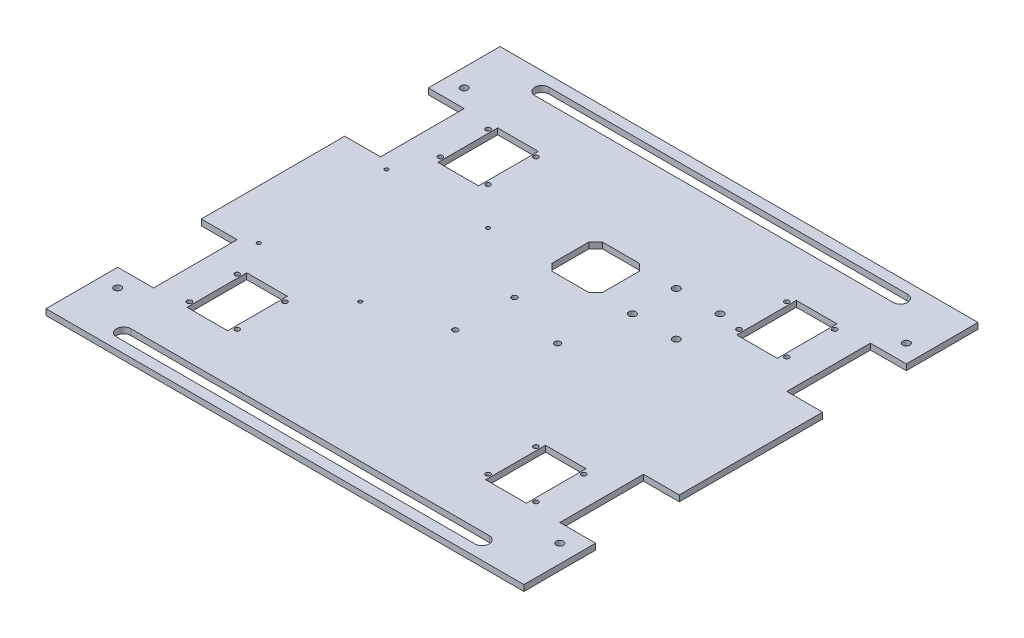
SolidWorks part; units mm, degrees
ref_plane "前基準面" through (0, 0, 0) normal (0, 0, 1) x (1, 0, 0)
ref_plane "上基準面" through (0, 0, 0) normal (0, 1, 0) x (1, 0, 0)
ref_plane "右基準面" through (0, 0, 0) normal (1, 0, 0) x (0, 0, -1)
sketch "草圖1" plane through (0, 0, 0) normal (0, 1, 0) x (1, 0, 0)
  line L0 (200, 190) -> (200, -190)
  line L1 (200, 190) -> (-200, 190)
  line L3 (200, -190) -> (-200, -190)
  line L4 (-200, 190) -> (-200, -190)
  line L5 (0, -190) -> (0, 190) construction
  line L6 (200, 0) -> (-200, 0) construction
  line L8 (-200, 130) -> (-200, -130) construction
  line L10 (-170, 130) -> (-170, -130) construction
  line L11 (-200, 130) -> (200, 130) construction
  line L12 (-200, 130) -> (-200, 190) construction
  line L13 (-200, 190) -> (200, 190) construction
  line L15 (-200, -130) -> (200, -130) construction
  line L16 (-200, -130) -> (-200, -190) construction
  line L17 (-200, -190) -> (200, -190) construction
  line L19 (170, 130) -> (170, -130) construction
  point P0 (0, 0)
  dimension "D1" = 400
  dimension "D2" = 260
  dimension "D3" = 60
  dimension "D4" = 60
  dimension "D5" = 30
extrude "填料-伸長1" add sketch "草圖1" along normal blind 5
sketch "草圖2" plane through (0, 5, 0) normal (0, 1, 0) x (1, 0, 0)
  line L0 (200, -190) -> (200, 190) construction
  line L1 (-200, 190) -> (200, 190) construction
  line L5 (-185, 190) -> (-185, -190) construction
  line L21 (-200, 190) -> (200, 190) construction
  line L22 (-200, 190) -> (-200, 130) construction
  line L23 (-200, 130) -> (200, 130) construction
  line L24 (-275.3304, 0) -> (275.3304, 0) construction
  line L25 (0, 247.3454) -> (0, -229.8147) construction
  line L42 (200, 190) -> (200, 130) construction
  line L44 (-41.25, 25) -> (41.25, 25) construction
  line L45 (-41.25, 25) -> (-41.25, -45) construction
  line L46 (-41.25, -45) -> (41.25, -45) construction
  line L47 (41.25, 25) -> (41.25, -45) construction
  line L59 (-200, 160) -> (200, 160) construction
  line L60 (-200, 145) -> (200, 145) construction
  line L61 (-200, -145) -> (200, -145) construction
  line L62 (-200, -160) -> (200, -160) construction
  line L63 (-200, -130) -> (200, -130) construction
  line L64 (200, -190) -> (200, -130) construction
  line L65 (-200, -190) -> (200, -190) construction
  line L66 (-200, -190) -> (-200, -130) construction
  line L67 (185, -190) -> (185, 190) construction
  line L68 (-200, 130) -> (-170, 130) construction
  line L69 (-200, 130) -> (-200, -130) construction
  line L70 (-200, -130) -> (-170, -130) construction
  line L71 (-170, 130) -> (-170, -130) construction
  line L72 (200, 130) -> (170, 130) construction
  line L73 (200, 130) -> (200, -130) construction
  line L74 (200, -130) -> (170, -130) construction
  line L75 (170, 130) -> (170, -130) construction
  line L76 (170, -60) -> (200, -60)
  line L77 (-200, 130) -> (-170, 130)
  line L78 (-200, 130) -> (-200, 60)
  line L79 (-200, 60) -> (-170, 60)
  line L80 (-170, 130) -> (-170, 60)
  line L81 (-170, -130) -> (-200, -130)
  line L82 (-170, -130) -> (-170, -60)
  line L83 (-170, -60) -> (-200, -60)
  line L84 (-200, -130) -> (-200, -60)
  line L85 (200, -130) -> (200, -60)
  line L86 (170, -130) -> (200, -130)
  line L87 (170, -130) -> (170, -60)
  line L88 (200, 60) -> (170, 60)
  line L89 (170, 130) -> (170, 60)
  line L90 (200, 130) -> (170, 130)
  line L91 (200, 130) -> (200, 60)
  line L100 (100, -80) -> (150, -80) construction
  line L101 (46.15, 91.35) -> (88.85, 91.35) construction
  line L102 (46.15, 91.35) -> (46.15, 48.65) construction
  line L103 (46.15, 48.65) -> (88.85, 48.65) construction
  line L104 (88.85, 91.35) -> (88.85, 48.65) construction
  line L105 (-150, -80) -> (-100, -80) construction
  line L106 (-150, -80) -> (-150, -130) construction
  line L107 (-150, -130) -> (-100, -130) construction
  line L108 (-100, -80) -> (-100, -130) construction
  line L109 (-142, -80) -> (-108, -80)
  line L110 (-142, -80) -> (-142, -130)
  line L111 (-142, -130) -> (-108, -130)
  line L112 (-108, -80) -> (-108, -130)
  line L113 (100, -80) -> (100, -130) construction
  line L114 (100, -130) -> (150, -130) construction
  line L115 (150, -80) -> (150, -130) construction
  line L116 (108, -80) -> (142, -80)
  line L117 (108, -80) -> (108, -130)
  line L118 (108, -130) -> (142, -130)
  line L119 (142, -80) -> (142, -130)
  line L120 (-150, 130) -> (-100, 130) construction
  line L121 (-150, 130) -> (-150, 80) construction
  line L122 (-150, 80) -> (-100, 80) construction
  line L123 (-100, 130) -> (-100, 80) construction
  line L124 (-142, 130) -> (-108, 130)
  line L125 (-142, 130) -> (-142, 80)
  line L126 (-142, 80) -> (-108, 80)
  line L127 (-108, 130) -> (-108, 80)
  line L128 (100, 130) -> (150, 130) construction
  line L129 (100, 130) -> (100, 80) construction
  line L130 (100, 80) -> (150, 80) construction
  line L131 (150, 130) -> (150, 80) construction
  line L132 (108, 130) -> (142, 130)
  line L133 (108, 130) -> (108, 80)
  line L134 (108, 80) -> (142, 80)
  line L135 (142, 130) -> (142, 80)
  line L136 (-21.15, 85.5) -> (-15.5, 91.15)
  line L137 (-72, -55) -> (-160, -55) construction
  line L138 (-72, -55) -> (-72, 55) construction
  line L139 (-72, 55) -> (-160, 55) construction
  line L140 (-160, -55) -> (-160, 55) construction
  line L141 (-15.5, 91.15) -> (15.5, 91.15)
  line L142 (-21.15, 85.5) -> (-21.15, 54.5)
  line L143 (-15.5, 48.85) -> (15.5, 48.85)
  line L144 (21.15, 85.5) -> (21.15, 54.5)
  line L145 (15.5, 91.15) -> (21.15, 85.5)
  line L146 (15.5, 48.85) -> (21.15, 54.5)
  line L147 (-21.15, 54.5) -> (-15.5, 48.85)
  line L148 (-234.8869, -145) -> (-234.8869, -175) construction
  line L149 (-214.8869, -145) -> (-214.8869, -175)
  line L150 (-254.8869, -145) -> (-254.8869, -175)
  line L151 (-234.8869, 145) -> (-234.8869, 175) construction
  line L152 (-214.8869, 145) -> (-214.8869, 175)
  line L153 (-254.8869, 145) -> (-254.8869, 175)
  line L154 (234.8869, -145) -> (234.8869, -175) construction
  line L155 (214.8869, -145) -> (214.8869, -175)
  line L156 (254.8869, -145) -> (254.8869, -175)
  line L157 (234.8869, 145) -> (234.8869, 175) construction
  line L158 (214.8869, 145) -> (214.8869, 175)
  line L159 (254.8869, 145) -> (254.8869, 175)
  line L160 (-150, 175) -> (150, 175) construction
  line L161 (-150, 181) -> (150, 181)
  line L162 (-150, 169) -> (150, 169)
  line L163 (-150, -175) -> (150, -175) construction
  line L164 (-150, -181) -> (150, -181)
  line L165 (-150, -169) -> (150, -169)
  circle A21 centre (-13.32, -34.13) radius 2.25
  circle A22 centre (-12.05, 14.13) radius 2.25
  circle A23 centre (39.25, -1.11) radius 2.5
  circle A32 centre (-185, 145) radius 3
  circle A33 centre (185, 145) radius 3
  circle A34 centre (-185, -145) radius 3
  circle A35 centre (185, -145) radius 3
  circle A40 centre (49.15, 88.35) radius 3
  circle A41 centre (85.85, 88.35) radius 3
  circle A42 centre (49.15, 51.65) radius 3
  circle A43 centre (85.85, 51.65) radius 3
  circle A44 centre (-145, -85) radius 2
  circle A45 centre (-105, -85) radius 2
  circle A46 centre (-145, -125) radius 2
  circle A47 centre (-105, -125) radius 2
  circle A48 centre (105, -85) radius 2
  circle A49 centre (145, -85) radius 2
  circle A50 centre (105, -125) radius 2
  circle A51 centre (145, -125) radius 2
  circle A52 centre (-145, 125) radius 2
  circle A53 centre (-105, 125) radius 2
  circle A54 centre (-145, 85) radius 2
  circle A55 centre (-105, 85) radius 2
  circle A56 centre (105, 125) radius 2
  circle A57 centre (145, 125) radius 2
  circle A58 centre (105, 85) radius 2
  circle A59 centre (145, 85) radius 2
  circle A60 centre (-158.45, 53.45) radius 1.55
  circle A61 centre (-73.55, 53.45) radius 1.55
  circle A62 centre (-158.45, -53.45) radius 1.55
  circle A63 centre (-73.55, -53.45) radius 1.55
  circle A64 centre (-15.5, 85.5) radius 1.5 construction
  circle A65 centre (15.5, 85.5) radius 1.5 construction
  circle A66 centre (-15.5, 54.5) radius 1.5 construction
  circle A67 centre (15.5, 54.5) radius 1.5 construction
  arc A68 (-214.8869, -145) -> (-254.8869, -145) centre (-234.8869, -145) ccw
  arc A69 (-254.8869, -175) -> (-214.8869, -175) centre (-234.8869, -175) ccw
  arc A70 (-214.8869, 145) -> (-254.8869, 145) centre (-234.8869, 145) cw
  arc A71 (-254.8869, 175) -> (-214.8869, 175) centre (-234.8869, 175) cw
  arc A72 (214.8869, -145) -> (254.8869, -145) centre (234.8869, -145) cw
  arc A73 (254.8869, -175) -> (214.8869, -175) centre (234.8869, -175) cw
  arc A74 (214.8869, 145) -> (254.8869, 145) centre (234.8869, 145) ccw
  arc A75 (254.8869, 175) -> (214.8869, 175) centre (234.8869, 175) ccw
  arc A76 (-150, 181) -> (-150, 169) centre (-150, 175) ccw
  arc A77 (150, 169) -> (150, 181) centre (150, 175) ccw
  arc A78 (-150, -181) -> (-150, -169) centre (-150, -175) cw
  arc A79 (150, -169) -> (150, -181) centre (150, -175) cw
  point P54 (0, 70)
  point P55 (0, 91.15)
  point P56 (-234.8869, -160)
  point P62 (0, -10)
  point P64 (-41.25, -10)
  point P70 (-234.8869, -125)
  point P71 (-234.8869, -195)
  point P73 (0, 175)
  point P89 (-234.8869, 160)
  point P102 (0, 25)
  point P175 (-116, 55)
  point P177 (-160, 0)
  point P182 (-116, 0)
  point P183 (67.5, 91.35)
  point P185 (46.15, 70)
  point P187 (234.8869, -160)
  point P191 (67.5, 70)
  point P195 (234.8869, 160)
  point P201 (0, 0)
  point P202 (63.1706, 70)
  point P203 (0, 0)
  point P204 (-21.15, 91.15)
  point P205 (21.15, 48.85)
  point P206 (-21.15, 48.85)
  point P207 (21.15, 91.15)
  point P223 (70.7591, 70)
  point P224 (-21.15, 70)
  point P227 (0, -175)
  point P232 (0, 0)
  point P233 (61.8475, 70)
  point P234 (61.5035, 70)
  point P235 (0, 0)
  point P236 (-113.75, 0)
  point P237 (0, 0)
  point P238 (-127.07, 30.0811)
  point P239 (-113.75, 9.3825)
  point P240 (-319.643, -20.8657)
  point P241 (0, 0)
  point P242 (0, 0)
  point P243 (0, -73.7908)
  point P244 (-331.693, 100.421)
  point P245 (0, -10.2807)
  point P246 (-307.7348, -10)
  point P247 (-120.7328, 0)
  dimension "D5" = 60
  dimension "D6" = 15
  dimension "D7" = 30
  dimension "D9" = 6
  dimension "D18" = 4.5
  dimension "D25" = 5
  dimension "D28" = 42.7
  dimension "D35" = 10
  dimension "D10" = 6
  dimension "D13" = 70
  dimension "D30" = 6
  dimension "D31" = 50
  dimension "D32" = 50
  dimension "D33" = 40
  dimension "D37" = 4
  dimension "D46" = 4
  dimension "D55" = 4
  dimension "D64" = 4
  dimension "D73" = 3.1
  dimension "D77" = 3
  dimension "D26" = 6
  dimension "D3" = 15
  dimension "D4" = 15
  dimension "D11" = 70
  dimension "D12" = 40
  dimension "D14" = 120
  dimension "D15" = 25
  dimension "D16" = 82.5
  dimension "D17" = 70
  dimension "D19" = 10.87
  dimension "D20" = 27.93
  dimension "D21" = 29.2
  dimension "D22" = 10.87
  dimension "D23" = 26.11
  dimension "D24" = 2
  dimension "D27" = 15
  dimension "D29" = 42.7
  dimension "D34" = 300
  dimension "D36" = 40
  dimension "D38" = 5
  dimension "D90" = 15
  dimension "D39" = 5
  dimension "D40" = 34
  dimension "D41" = 8
  dimension "D42" = 50
  dimension "D43" = 50
  dimension "D44" = 40
  dimension "D45" = 40
  dimension "D47" = 5
  dimension "D48" = 5
  dimension "D49" = 34
  dimension "D50" = 8
  dimension "D51" = 50
  dimension "D52" = 50
  dimension "D53" = 40
  dimension "D54" = 40
  dimension "D56" = 5
  dimension "D57" = 5
  dimension "D58" = 34
  dimension "D59" = 8
  dimension "D60" = 50
  dimension "D61" = 50
  dimension "D62" = 40
  dimension "D63" = 40
  dimension "D65" = 5
  dimension "D66" = 5
  dimension "D67" = 34
  dimension "D68" = 8
  dimension "D69" = 20
  dimension "D70" = 20
  dimension "D71" = 88
  dimension "D72" = 110
  dimension "D74" = 10
  dimension "D75" = 42.3
  dimension "D76" = 42.3
  dimension "D78" = 31
  dimension "D79" = 31
  dimension "D80" = 5.65
  dimension "D81" = 5.65
  dimension "D82" = 5.65
  dimension "D83" = 5.65
  dimension "D84" = 5.65
  dimension "D85" = 5.65
  dimension "D86" = 5.65
  dimension "D87" = 5.65
  dimension "D88" = 5.65
  dimension "D89" = 5.65
extrude "除料-伸長1" cut sketch "草圖2" against normal through all
